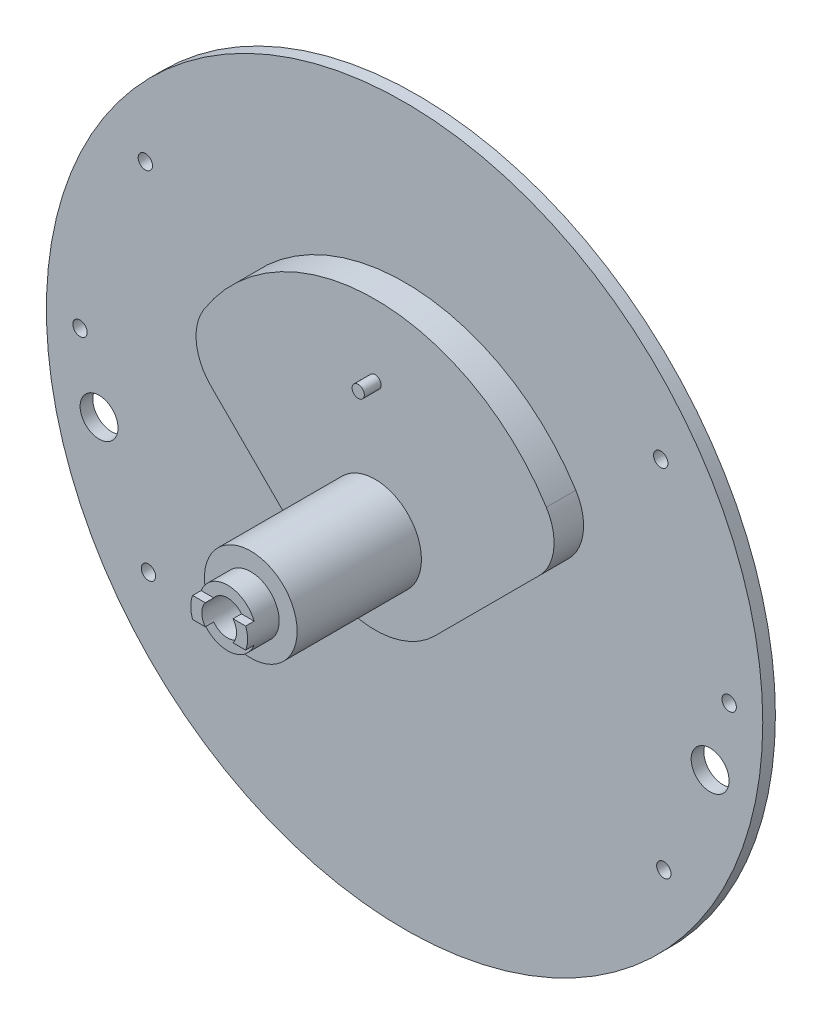
SolidWorks part; units mm, degrees
ref_plane "Plan de face" through (0, 0, 0) normal (0, 0, 1) x (1, 0, 0)
ref_plane "Plan de dessus" through (0, 0, 0) normal (0, 1, 0) x (1, 0, 0)
ref_plane "Plan de droite" through (0, 0, 0) normal (1, 0, 0) x (0, 0, -1)
sketch "Esquisse1" plane through (0, 0, 0) normal (0, 0, 1) x (1, 0, 0)
  circle A0 centre (0, 0) radius 85
  circle A1 centre (0, 0) radius 7.5
  circle A2 centre (-72.5, -16) radius 4.5
  circle A3 centre (72.5, -16) radius 4.5
  dimension "D1" = 170
  dimension "D2" = 15
  dimension "D3" = 9
  dimension "D4" = 9
  dimension "D5" = 145
  dimension "D7" = 16
  dimension "D6" = 72.5
extrude "Boss.-Extru.1" add sketch "Esquisse1" along normal blind 3
sketch "Esquisse3" plane through (0, 0, 3) normal (0, 0, 1) x (1, 0, 0)
  line L10 (14.1421, -14.1421) -> (38.9615, 10.6772)
  line L11 (-38.9615, 10.6772) -> (-14.1421, -14.1421)
  line L12 (-36.8402, 12.7985) -> (-12.0208, -12.0208)
  line L13 (12.0208, -12.0208) -> (36.8402, 12.7985)
  arc A17 (38.0953, 23.9531) -> (-38.0953, 23.9531) centre (0, 0) ccw
  arc A24 (38.9615, 10.6772) -> (40.6349, 25.55) centre (30.4762, 19.1625) ccw
  arc A25 (-14.1421, -14.1421) -> (14.1421, -14.1421) centre (0, 0) ccw
  arc A26 (-40.6349, 25.55) -> (-38.9615, 10.6772) centre (-30.4762, 19.1625) ccw
  arc A27 (40.6349, 25.55) -> (-40.6349, 25.55) centre (0, 0) ccw
  arc A29 (-38.0953, 23.9531) -> (-36.8402, 12.7985) centre (-30.4762, 19.1625) ccw
  arc A30 (-12.0208, -12.0208) -> (12.0208, -12.0208) centre (0, 0) ccw
  arc A31 (36.8402, 12.7985) -> (38.0953, 23.9531) centre (30.4762, 19.1625) ccw
extrude "Boss.-Extru.2" add sketch "Esquisse3" along normal blind 4
sketch "Esquisse4" plane through (0, 0, 7) normal (0, 0, 1) x (1, 0, 0)
  line L0 (-38.9615, 10.6772) -> (-14.1421, -14.1421) construction
  line L1 (-38.9615, 10.6772) -> (-14.1421, -14.1421)
  line L2 (14.1421, -14.1421) -> (38.9615, 10.6772) construction
  line L3 (14.1421, -14.1421) -> (38.9615, 10.6772)
  arc A0 (40.6349, 25.55) -> (-40.6349, 25.55) centre (0, 0) ccw construction
  arc A1 (40.6349, 25.55) -> (-40.6349, 25.55) centre (0, 0) ccw
  arc A2 (-40.6349, 25.55) -> (-38.9615, 10.6772) centre (-30.4762, 19.1625) ccw construction
  arc A3 (-40.6349, 25.55) -> (-38.9615, 10.6772) centre (-30.4762, 19.1625) ccw
  arc A4 (-14.1421, -14.1421) -> (14.1421, -14.1421) centre (0, 0) ccw construction
  arc A5 (-14.1421, -14.1421) -> (14.1421, -14.1421) centre (0, 0) ccw
  arc A6 (38.9615, 10.6772) -> (40.6349, 25.55) centre (30.4762, 19.1625) ccw construction
  arc A7 (38.9615, 10.6772) -> (40.6349, 25.55) centre (30.4762, 19.1625) ccw
extrude "Boss.-Extru.3" add sketch "Esquisse4" along normal blind 3
sketch "Esquisse5" plane through (0, 0, 7) normal (0, 0, -1) x (-1, 0, 0)
  circle A0 centre (0, 0) radius 7.5 construction
  circle A1 centre (0, 0) radius 7.5
extrude "Enlèv. mat.-Extru.2" cut sketch "Esquisse5" against normal blind 3
sketch "Esquisse6" plane through (0, 0, 3) normal (0, 0, 1) x (1, 0, 0)
  line L2 (-36.8402, 12.7985) -> (-12.0208, -12.0208)
  line L3 (12.0208, -12.0208) -> (36.8402, 12.7985)
  line L4 (-36.8402, 12.7985) -> (-12.0208, -12.0208)
  line L5 (12.0208, -12.0208) -> (36.8402, 12.7985)
  arc A4 (36.8402, 12.7985) -> (38.0953, 23.9531) centre (30.4762, 19.1625) ccw
  arc A5 (38.0953, 23.9531) -> (-38.0953, 23.9531) centre (0, 0) ccw
  arc A6 (-38.0953, 23.9531) -> (-36.8402, 12.7985) centre (-30.4762, 19.1625) ccw
  arc A7 (-12.0208, -12.0208) -> (12.0208, -12.0208) centre (0, 0) ccw
  arc A8 (36.8402, 12.7985) -> (38.0953, 23.9531) centre (30.4762, 19.1625) ccw
  arc A9 (38.0953, 23.9531) -> (-38.0953, 23.9531) centre (0, 0) ccw
  arc A10 (-38.0953, 23.9531) -> (-36.8402, 12.7985) centre (-30.4762, 19.1625) ccw
  arc A11 (-12.0208, -12.0208) -> (12.0208, -12.0208) centre (0, 0) ccw
  dimension "D1" = 0
extrude "Enlèv. mat.-Extru.3" cut sketch "Esquisse6" against normal blind 3
ref_axis "Axe1" through (0, 0, 37.0012) along (0, 0, -1)
sketch "Esquisse7" plane through (0, 0, 0) normal (1, 0, 0) x (0, 0, -1)
  line L0 (-7, -7.5) -> (-38.5, -5.12)
  line L1 (-38.5, -5.12) -> (-38.5, -4.12)
  line L2 (-38.5, -4.12) -> (-47, -4.12)
  line L3 (-47, -4.12) -> (-47, -11)
  line L4 (-47, -11) -> (-7, -11)
  line L5 (-7, -11) -> (-7, -7.5)
  line L6 (0, 0) -> (-39.1661, 0) construction
  dimension "D1" = 22
  dimension "D2" = 8.24
  dimension "D3" = 1
  dimension "D4" = 31.5
  dimension "D5" = 40
revolve "Révolution1" add sketch "Esquisse7" angle 360 about L6
sketch "Esquisse8" plane through (0, 0, 47) normal (0, 0, 1) x (1, 0, 0)
  line L0 (3.2937, 2.475) -> (10.7179, 2.475)
  line L1 (-10.7179, 2.475) -> (-3.2937, 2.475)
  line L3 (-10.7179, -2.475) -> (-3.2937, -2.475)
  line L5 (3.2937, -2.475) -> (10.7179, -2.475)
  circle A1 centre (0, 0) radius 4.12 construction
  circle A2 centre (0, 0) radius 11 construction
  arc A3 (-10.7179, -2.475) -> (10.7179, -2.475) centre (0, 0) ccw
  arc A4 (-3.2937, -2.475) -> (3.2937, -2.475) centre (0, 0) ccw
  arc A5 (10.7179, 2.475) -> (-10.7179, 2.475) centre (0, 0) ccw
  arc A6 (3.2937, 2.475) -> (-3.2937, 2.475) centre (0, 0) ccw
  dimension "D1" = 4.95
  dimension "D2" = 2.475
extrude "Enlèv. mat.-Extru.6" cut sketch "Esquisse8" against normal blind 2
sketch "Esquisse9" plane through (0, 0, 7) normal (0, 0, -1) x (-1, 0, 0)
  arc A0 (-12.0208, -12.0208) -> (12.0208, -12.0208) centre (0, 0) ccw construction
  circle A1 centre (0, 0) radius 17
extrude "Enlèv. mat.-Extru.4" cut sketch "Esquisse9" against normal blind 0.25
sketch "Esquisse10" plane through (0, 0, 47) normal (0, 0, 1) x (1, 0, 0)
  circle A0 centre (0, 0) radius 6.75
  dimension "D1" = 13.5
extrude "Enlèv. mat.-Extru.5" cut sketch "Esquisse10" against normal blind 7.5 and the other way blind 10 flip side to cut
sketch "Esquisse11" plane through (0, 0, 10) normal (0, 0, 1) x (1, 0, 0)
  circle A0 centre (0, 31.05) radius 1.45
  dimension "D1" = 2.9
  dimension "D2" = 31.05
extrude "Boss.-Extru.4" add sketch "Esquisse11" along normal blind 4
hole_wizard "Dégagement M31" positions "Esquisse13" profile "Esquisse12" hole size "M3" standard "ISO" end condition through all
sketch "Esquisse13" plane through (0, 0, 3) normal (0, 0, 1) x (1, 0, 0)
  point P0 (60.785, 42)
  point P1 (77.0199, 0)
  point P3 (61.5199, -42)
  point P5 (-60.785, -42)
  point P7 (-77.0199, 0)
  point P9 (-61.5199, 42)
sketch "Esquisse12" plane through (60.785, 42, 3) normal (1, 0, 0) x (0, -1, 0)
  line L0 (0, 0) -> (0, 3)
  line L1 (0, 3) -> (1.7, 3)
  line L2 (1.7, 3) -> (1.7, 0)
  line L5 (1.7, 0) -> (0, 0)
  line L11 (0, -6.35) -> (0, 107.95) construction
  dimension "Diamètre du perçage jusqu'au prochain" = 3.4
  dimension "Profondeur du perçage jusqu'au prochain" = 3
